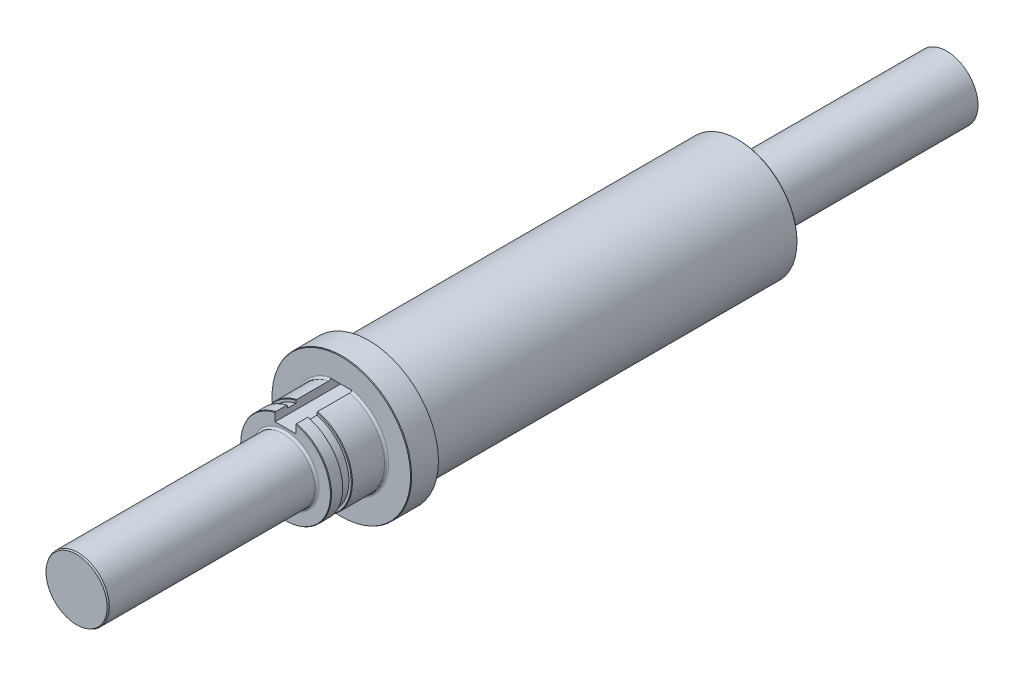
SolidWorks part; units mm, degrees
ref_plane "Front Plane" through (0, 0, 0) normal (0, 0, 1) x (1, 0, 0)
ref_plane "Top Plane" through (0, 0, 0) normal (0, 1, 0) x (1, 0, 0)
ref_plane "Right Plane" through (0, 0, 0) normal (1, 0, 0) x (0, 0, -1)
sketch "Sketch1" plane through (0, 0, 0) normal (0, 0, 1) x (1, 0, 0)
  circle A0 centre (0, 0) radius 4.5
  dimension "D1" = 9
extrude "Boss-Extrude1" add sketch "Sketch1" against normal blind 125
ref_plane "Plane1" through (0, 0, -30) normal (0, 0, 1) x (1, 0, 0)
sketch "Sketch2" plane through (0, 0, -30) normal (0, 0, 1) x (1, 0, 0)
  circle A0 centre (0, 0) radius 6.5
extrude "Boss-Extrude2" add sketch "Sketch2" against normal blind 65
ref_plane "Plane2" through (0, 0, -38) normal (0, 0, 1) x (1, 0, 0)
sketch "Sketch3" plane through (0, 0, -38) normal (0, 0, 1) x (1, 0, 0)
  circle A0 centre (0, 0) radius 10
  dimension "D1" = 20
extrude "Boss-Extrude3" add sketch "Sketch3" against normal blind 4
sketch "Sketch4" plane through (0, 0, -38) normal (0, 0, 1) x (1, 0, 0)
  line L1 (0, 0) -> (0, 16.1928) construction
  point P10 (0, 9.0272)
sketch "Sketch5" plane through (0, 0, -30) normal (0, 0, 1) x (1, 0, 0)
  line L0 (1.5, 6.5) -> (-1.5, 6.5)
  line L1 (0, 0) -> (0, 16.1928) construction
  line L2 (-1.5, 6.5) -> (-1.5, 5.1)
  line L3 (-1.5, 5.1) -> (1.5, 5.1)
  line L4 (0, 0) -> (0, 16.1928) construction
  line L5 (1.5, 6.5) -> (1.5, 5.1)
  circle A0 centre (0, 0) radius 6.5 construction
  point P13 (0, 5.1)
  point P14 (0, 6.5)
extrude "Cut-Extrude1" cut sketch "Sketch5" against normal blind 15
sketch "Sketch6" plane through (0, 0, 0) normal (0, 1, 0) x (1, 0, 0)
  line L0 (-6.1, 33) -> (-6.1, 31.75)
  line L3 (-7.5, 38) -> (-7.5, 33) construction
  line L4 (-6.5, 38) -> (6.5, 38) construction
  line L8 (-10, 38) -> (10, 38) construction
  line L9 (-7.5, 33) -> (-6.1, 33)
  line L10 (-6.1, 31.75) -> (-7.5, 31.75)
  line L11 (-7.5, 31.75) -> (-7.5, 33)
  line L12 (0, 0) -> (0, 28.6278) construction
  dimension "D1" = 1.25
  dimension "D2" = 5
revolve "Cut-Revolve1" cut sketch "Sketch6" angle 360 about L12
fillet "Fillet2" radius 0.3 1 edges at (4.5, 0, -30)
chamfer "Chamfer5" distance 0.1 angle 30 1 edges at (0, -6.5, -30) first distance on face at (0, -0.0877, -30.875)
chamfer "Chamfer6" distance 0.1 angle 30 1 edges at (0, -6.5, -33) first distance on face at (0, -0.0877, -35.5)
chamfer "Chamfer7" distance 0.1 angle 30 1 edges at (0, -6.5, -31.75) first distance on face at (0, -0.0907, -31.75)
chamfer "Chamfer8" distance 0.1 angle 30 1 edges at (10, 0, -38) first distance on face at (10, 0, -42)
fillet "Fillet4" radius 0.3 1 edges at (0, -6.5, -38)
chamfer "Chamfer9" distance 0.1 angle 30 1 edges at (10, 0, -42) first distance on face at (0, 3.2061, -42)
fillet "Fillet6" radius 0.3 1 edges at (4.5, 0, -95)
chamfer "Chamfer10" distance 0.2 angle 30 1 edges at (4.5, 0, -125) first distance on face at (4.5, 0, -125)
chamfer "Chamfer11" distance 0.2 angle 30 1 edges at (4.5, 0, 0) first distance on face at (4.5, 0, -29.7)
sketch "Sketch7" plane through (0, 0, -42) normal (0, 0, -1) x (-1, 0, 0)
  circle A0 centre (0, 0) radius 8.5
  dimension "D1" = 17
extrude "Boss-Extrude4" add sketch "Sketch7" along normal up to surface (53 mm away) up to face at (4.8, 0, -95)
chamfer "Chamfer12" distance 0.1 angle 45 1 edges at (8.5, 0, -95)
fillet "Fillet7" radius 0.3 1 edges at (8.5, 0, -42)
